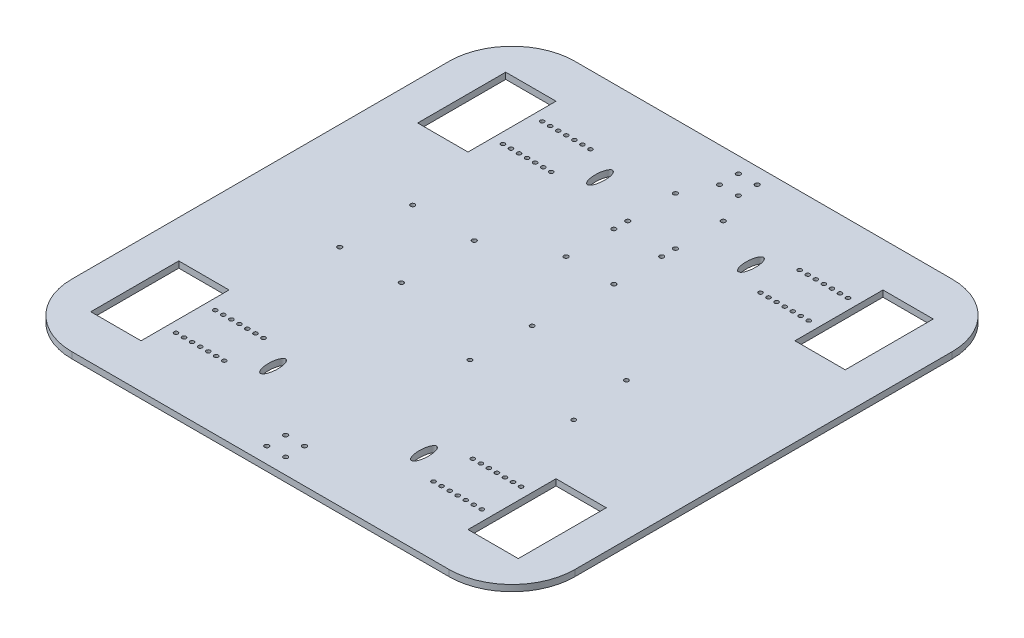
SolidWorks part; units mm, degrees
ref_plane "Front Plane" through (0, 0, 0) normal (0, 0, 1) x (1, 0, 0)
ref_plane "Top Plane" through (0, 0, 0) normal (0, 1, 0) x (1, 0, 0)
ref_plane "Right Plane" through (0, 0, 0) normal (1, 0, 0) x (0, 0, -1)
sketch "Sketch1" plane through (0, 0, 0) normal (0, 1, 0) x (1, 0, 0)
  line L0 (0, -1000) -> (0, 49000) construction
  line L1 (-170, 165) -> (-130, 165)
  line L2 (-170, 165) -> (-170, 95)
  line L3 (-170, 95) -> (-130, 95)
  line L4 (-130, 165) -> (-130, 95)
  line L5 (170, 95) -> (130, 95)
  line L6 (130, 165) -> (130, 95)
  line L7 (170, 165) -> (130, 165)
  line L8 (170, 165) -> (170, 95)
  line L9 (-1000, 0) -> (49000, 0) construction
  line L10 (-10, 190) -> (10, 190)
  line L11 (-10, 190) -> (-10, 170)
  line L12 (-10, 170) -> (10, 170)
  line L13 (10, 190) -> (10, 170)
  line L14 (-1010, 180) -> (48990, 180) construction
  line L15 (-1010, -180) -> (48990, -180) construction
  line L16 (0, 1000) -> (0, -49000) construction
  line L17 (-10, -170) -> (10, -170)
  line L18 (10, -190) -> (10, -170)
  line L19 (-10, -190) -> (10, -190)
  line L20 (-10, -190) -> (-10, -170)
  line L21 (170, -165) -> (170, -95)
  line L22 (-200, 200) -> (200, 200)
  line L23 (-200, 200) -> (-200, -200)
  line L24 (-200, -200) -> (200, -200)
  line L25 (200, 200) -> (200, -200)
  line L26 (170, -165) -> (130, -165)
  line L27 (130, -165) -> (130, -95)
  line L28 (170, -95) -> (130, -95)
  line L29 (-170, -95) -> (-130, -95)
  line L30 (-130, -165) -> (-130, -95)
  line L31 (-170, -165) -> (-130, -165)
  line L32 (-170, -165) -> (-170, -95)
  circle A0 centre (0, 0) radius 200 construction
  circle A1 centre (-7.5, 187.5) radius 1.75
  circle A2 centre (7.5, 187.5) radius 1.75
  circle A3 centre (7.5, 172.5) radius 1.75
  circle A4 centre (-7.5, 172.5) radius 1.75
  circle A5 centre (7.5, -187.5) radius 1.75
  circle A6 centre (-7.5, -187.5) radius 1.75
  circle A7 centre (-7.5, -172.5) radius 1.75
  circle A8 centre (7.5, -172.5) radius 1.75
  point P8 (-150, 165)
  point P19 (0, 190)
  point P22 (-10, 180)
  dimension "D1" = 400
  dimension "D7" = 3.5
  dimension "D2" = 40
  dimension "D3" = 70
  dimension "D4" = 150
  dimension "D5" = 20
  dimension "D6" = 180
  dimension "D8" = 2.5
  dimension "D9" = 2.5
  dimension "D10" = 35
extrude "Boss-Extrude2" add sketch "Sketch1" along normal blind 5 contours L25 L22 L23 L24 L1 L4 L3 L2 L7 L8 L5 L6 L10 L13 L12 L11 L19 L20 L17 L18 | L20 L19 L18 L17 A6 A5 A7 A8 | L13 L10 L11 L12 A2 A1 A3 A4 region at (0, 0, -180) region at (0, 0, 180) region at (0, 0, 0)
fillet "Fillet1" radius 50 4 edges at (200, 2.5, -200) (200, 2.5, 200) (-200, 2.5, 200) (-200, 2.5, -200)
sketch "Sketch2" plane through (0, 5, 0) normal (0, 1, 0) x (1, 0, 0)
  line L0 (-1094.0419, 130) -> (48905.9581, 130) construction
  line L1 (-130, 148.8) -> (-78.5, 148.8) construction
  line L2 (-130, 148.8) -> (-130, 111.2) construction
  line L3 (-130, 111.2) -> (-78.5, 111.2) construction
  line L4 (-78.5, 148.8) -> (-78.5, 111.2) construction
  line L5 (-130, 165) -> (-130, 95) construction
  line L6 (-170, 165) -> (-170, 95) construction
  line L7 (0, -1000) -> (0, 49000) construction
  line L8 (130, 111.2) -> (78.5, 111.2) construction
  line L9 (78.5, 148.8) -> (78.5, 111.2) construction
  line L10 (130, 148.8) -> (78.5, 148.8) construction
  line L11 (130, 148.8) -> (130, 111.2) construction
  line L12 (-1000, 0) -> (49000, 0) construction
  line L13 (130, -148.8) -> (130, -111.2) construction
  line L14 (130, -148.8) -> (78.5, -148.8) construction
  line L15 (78.5, -148.8) -> (78.5, -111.2) construction
  line L16 (130, -111.2) -> (78.5, -111.2) construction
  line L17 (-78.5, -148.8) -> (-78.5, -111.2) construction
  line L18 (-130, -111.2) -> (-78.5, -111.2) construction
  line L19 (-130, -148.8) -> (-130, -111.2) construction
  line L20 (-130, -148.8) -> (-78.5, -148.8) construction
  line L21 (-1094.0419, -130) -> (48905.9581, -130) construction
  circle A0 centre (-121.6, 145.6) radius 1.6
  circle A1 centre (-115.2, 145.6) radius 1.6
  circle A2 centre (-108.8, 145.6) radius 1.6
  circle A3 centre (-102.4, 145.6) radius 1.6
  circle A4 centre (-96, 145.6) radius 1.6
  circle A5 centre (-89.6, 145.6) radius 1.6
  circle A6 centre (-83.2, 145.6) radius 1.6
  circle A7 centre (-83.2, 114.4) radius 1.6
  circle A8 centre (-89.6, 114.4) radius 1.6
  circle A9 centre (-96, 114.4) radius 1.6
  circle A10 centre (-102.4, 114.4) radius 1.6
  circle A11 centre (-108.8, 114.4) radius 1.6
  circle A12 centre (-115.2, 114.4) radius 1.6
  circle A13 centre (-121.6, 114.4) radius 1.6
  circle A14 centre (83.2, 114.4) radius 1.6
  circle A15 centre (89.6, 114.4) radius 1.6
  circle A16 centre (96, 114.4) radius 1.6
  circle A17 centre (102.4, 114.4) radius 1.6
  circle A18 centre (108.8, 114.4) radius 1.6
  circle A19 centre (115.2, 114.4) radius 1.6
  circle A20 centre (121.6, 114.4) radius 1.6
  circle A21 centre (83.2, 145.6) radius 1.6
  circle A22 centre (89.6, 145.6) radius 1.6
  circle A23 centre (96, 145.6) radius 1.6
  circle A24 centre (102.4, 145.6) radius 1.6
  circle A25 centre (108.8, 145.6) radius 1.6
  circle A26 centre (115.2, 145.6) radius 1.6
  circle A27 centre (121.6, 145.6) radius 1.6
  circle A28 centre (121.6, -145.6) radius 1.6
  circle A29 centre (115.2, -145.6) radius 1.6
  circle A30 centre (108.8, -145.6) radius 1.6
  circle A31 centre (102.4, -145.6) radius 1.6
  circle A32 centre (96, -145.6) radius 1.6
  circle A33 centre (89.6, -145.6) radius 1.6
  circle A34 centre (83.2, -145.6) radius 1.6
  circle A35 centre (121.6, -114.4) radius 1.6
  circle A36 centre (115.2, -114.4) radius 1.6
  circle A37 centre (108.8, -114.4) radius 1.6
  circle A38 centre (102.4, -114.4) radius 1.6
  circle A39 centre (96, -114.4) radius 1.6
  circle A40 centre (89.6, -114.4) radius 1.6
  circle A41 centre (83.2, -114.4) radius 1.6
  circle A42 centre (-121.6, -114.4) radius 1.6
  circle A43 centre (-115.2, -114.4) radius 1.6
  circle A44 centre (-108.8, -114.4) radius 1.6
  circle A45 centre (-102.4, -114.4) radius 1.6
  circle A46 centre (-96, -114.4) radius 1.6
  circle A47 centre (-89.6, -114.4) radius 1.6
  circle A48 centre (-83.2, -114.4) radius 1.6
  circle A49 centre (-83.2, -145.6) radius 1.6
  circle A50 centre (-89.6, -145.6) radius 1.6
  circle A51 centre (-96, -145.6) radius 1.6
  circle A52 centre (-102.4, -145.6) radius 1.6
  circle A53 centre (-108.8, -145.6) radius 1.6
  circle A54 centre (-115.2, -145.6) radius 1.6
  circle A55 centre (-121.6, -145.6) radius 1.6
  point P9 (-130, 130)
  point P40 (-170, 130)
  dimension "D3" = 3.2
  dimension "D7" = 6.4
  dimension "D5" = 8.4
  dimension "D1" = 37.6
  dimension "D2" = 4.7
  dimension "D4" = 31.2
  dimension "D6" = 7
extrude "Cut-Extrude1" cut sketch "Sketch2" against normal blind 5
sketch "Sketch3" plane through (0, 5, 0) normal (0, 1, 0) x (1, 0, 0)
  line L0 (-150, -200) -> (150, -200) construction
  line L1 (0, 3.34) -> (101.6, 3.34) construction
  line L2 (0, 3.34) -> (0, -50) construction
  line L3 (0, -50) -> (101.6, -50) construction
  line L4 (101.6, 3.34) -> (101.6, -50) construction
  line L5 (-200, 150) -> (-200, -150) construction
  circle A0 centre (13.97, -47.46) radius 1.65
  circle A1 centre (15.24, 0.8) radius 1.65
  circle A2 centre (96.52, -47.46) radius 1.65
  circle A3 centre (90.17, 0.8) radius 1.65
  dimension "D5" = 3.3
  dimension "D8" = 3.3
  dimension "D9" = 96.52
  dimension "D10" = 90.17
  dimension "D1" = 101.6
  dimension "D2" = 53.34
  dimension "D3" = 13.97
  dimension "D4" = 2.54
  dimension "D6" = 15.24
  dimension "D7" = 50.8
  dimension "D11" = 150
  dimension "D12" = 200
extrude "Cut-Extrude2" cut sketch "Sketch3" against normal blind 10 contours A1 | A2 | L2 L1 L4 L3 | A0 | A3 region at (15.24, 5, -0.8) region at (96.52, 5, 47.46)
sketch "Sketch4" plane through (0, 5, 0) normal (0, 1, 0) x (1, 0, 0)
  line L0 (-19, 149) -> (19, 149) construction
  line L1 (-1149.7342, 130) -> (48850.2658, 130) construction
  line L2 (-22, 152) -> (22, 152) construction
  line L3 (-22, 152) -> (-22, 108) construction
  line L4 (-22, 108) -> (22, 108) construction
  line L5 (22, 152) -> (22, 108) construction
  line L6 (-19, 111) -> (19, 111) construction
  line L7 (-19, 100) -> (19, 100) construction
  line L8 (-1231.3219, 81) -> (48768.6781, 81) construction
  line L9 (-22, 103) -> (22, 103) construction
  line L10 (-22, 103) -> (-22, 59) construction
  line L11 (-22, 59) -> (22, 59) construction
  line L12 (22, 103) -> (22, 59) construction
  line L13 (-19, 62) -> (19, 62) construction
  line L16 (-130, 165) -> (-130, 95) construction
  line L17 (-150, 200) -> (150, 200) construction
  circle A0 centre (-19, 149) radius 1.75
  circle A1 centre (19, 149) radius 1.75
  circle A2 centre (19, 111) radius 1.75
  circle A3 centre (-19, 111) radius 1.75
  circle A4 centre (-19, 100) radius 1.75
  circle A5 centre (19, 100) radius 1.75
  circle A6 centre (19, 62) radius 1.75
  circle A7 centre (-19, 62) radius 1.75
  point P9 (0, 149)
  point P10 (0, 152)
  point P14 (-22, 130)
  point P26 (0, 100)
  point P27 (0, 103)
  point P31 (-22, 81)
  point P38 (-130, 130)
  point P39 (0, 200)
  point P40 (0, 108)
  dimension "D1" = 3.5
  dimension "D5" = 3.5
  dimension "D2" = 38
  dimension "D3" = 44
  dimension "D4" = 38
  dimension "D6" = 38
  dimension "D7" = 44
  dimension "D8" = 38
  dimension "D9" = 5
extrude "Cut-Extrude3" cut sketch "Sketch4" against normal blind 10
sketch "Sketch5" plane through (0, 5, 0) normal (0, 1, 0) x (1, 0, 0)
  line L0 (-1081.3236, 7.5) -> (48918.6764, 7.5) construction
  line L1 (-119, -45) -> (-63, -45) construction
  line L2 (-119, -45) -> (-119, 40) construction
  line L3 (-119, 40) -> (-63, 40) construction
  line L4 (-63, -45) -> (-63, 40) construction
  line L5 (-125, -50) -> (-57, -50) construction
  line L6 (-125, -50) -> (-125, 45) construction
  line L7 (-125, 45) -> (-57, 45) construction
  line L8 (-57, -50) -> (-57, 45) construction
  line L9 (-200, 150) -> (-200, -150) construction
  line L10 (-150, -200) -> (150, -200) construction
  circle A0 centre (-115.5, 36.5) radius 1.75
  circle A1 centre (-66.5, 36.5) radius 1.75
  circle A2 centre (-66.5, -21.5) radius 1.75
  circle A3 centre (-115.5, -21.5) radius 1.75
  dimension "D4" = 3.5
  dimension "D5" = 3.5
  dimension "D1" = 85
  dimension "D2" = 56
  dimension "D3" = 49
  dimension "D6" = 3.5
  dimension "D7" = 58
  dimension "D8" = 3.5
  dimension "D9" = 5
  dimension "D10" = 5
  dimension "D11" = 6
  dimension "D12" = 6
  dimension "D13" = 75
  dimension "D14" = 150
extrude "Cut-Extrude4" cut sketch "Sketch5" against normal blind 10
sketch "Sketch6" plane through (0, 5, 0) normal (0, 1, 0) x (1, 0, 0)
  line L0 (-130, 165) -> (-130, 95) construction
  line L1 (0, -800) -> (0, 49200) construction
  line L2 (-150, 200) -> (150, 200) construction
  line L3 (-1200, 0) -> (48800, 0) construction
  line L4 (-200, 150) -> (-200, -150) construction
  ellipse E0 centre (-60, 130) end of major axis (-60, 120) minor radius 3.75
  ellipse E1 centre (60, 130) end of major axis (60, 140) minor radius 3.75
  ellipse E2 centre (60, -130) end of major axis (60, -140) minor radius 3.75
  ellipse E3 centre (-60, -130) end of major axis (-60, -140) minor radius 3.75
  point P13 (-130, 130)
  point P14 (-200, 0)
  point P26 (0, 200)
  dimension "D1" = 70
  dimension "D2" = 20
  dimension "D3" = 7.5
extrude "Cut-Extrude5" cut sketch "Sketch6" against normal blind 10
